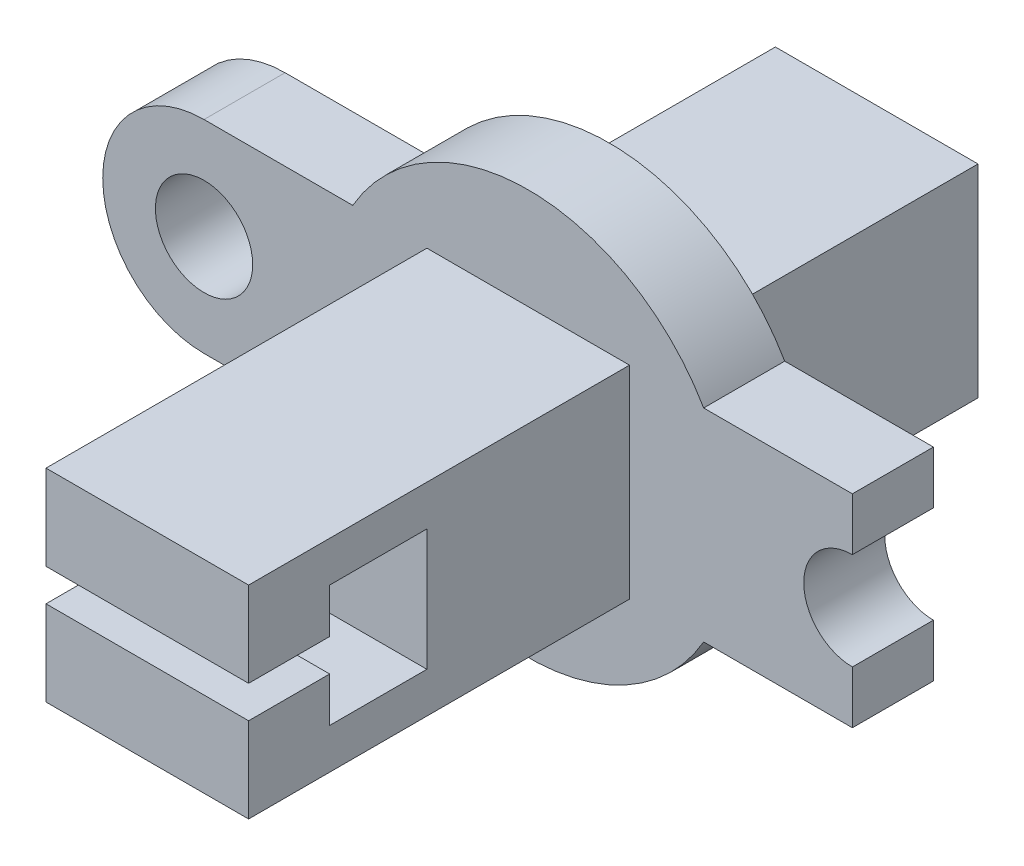
SolidWorks part; units mm, degrees
ref_plane "Спереди" through (0, 0, 0) normal (0, 0, 1) x (1, 0, 0)
ref_plane "Сверху" through (0, 0, 0) normal (0, 1, 0) x (1, 0, 0)
ref_plane "Справа" through (0, 0, 0) normal (1, 0, 0) x (0, 0, -1)
sketch "Эскиз1" plane through (0, 0, 0) normal (0, 0, 1) x (1, 0, 0)
  line L0 (-40, 12.5) -> (-21.6506, 12.5)
  line L1 (-12.5, -12.5) -> (12.5, -12.5)
  line L2 (-12.5, -12.5) -> (-12.5, 12.5)
  line L3 (-12.5, 12.5) -> (12.5, 12.5)
  line L4 (12.5, -12.5) -> (12.5, 12.5)
  line L5 (-12.5, -12.5) -> (12.5, 12.5) construction
  line L6 (-12.5, 12.5) -> (12.5, -12.5) construction
  line L7 (-40, -12.5) -> (-21.6506, -12.5)
  line L8 (0, 0) -> (0, 25) construction
  line L9 (40, -12.5) -> (21.6506, -12.5)
  line L10 (40, 12.5) -> (21.6506, 12.5)
  line L11 (40, -6) -> (40, -12.5)
  line L12 (40, 6) -> (40, 12.5)
  circle A0 centre (0, 0) radius 25
  circle A1 centre (-40, 0) radius 12.5
  circle A2 centre (-40, 0) radius 6
  circle A3 centre (40, 0) radius 6
  circle A4 centre (40, 0) radius 12.5
  circle A5 centre (0, -25) radius 5
  point P0 (0, 0)
  dimension "D2" = 50
  dimension "D3" = 25
  dimension "D5" = 12
  dimension "D6" = 10
  dimension "D1" = 25
  dimension "D4" = 40
extrude "Бобышка-Вытянуть1" add sketch "Эскиз1" along normal blind 90 contours L1 L4 L3 L2 region at (0, 0, 0)
extrude "Бобышка-Вытянуть2" add sketch "Эскиз1<3>" along normal blind 10 from offset 33 contours A0 L4 L1 L2 L3 | A1 L7 A0 L0 | A1 A2 | L9 A4 L10 A0 | A4 L11 A3 L12 | A0 A5 region at (-30.8253, 12.1899, 0) region at (-31.4112, 8.5888, 0) region at (0, 24.2964, 0) region at (30.8253, 12.1899, 0) region at (33.869, 0, 0) region at (0, -22.7904, 0)
sketch "Эскиз1<3>" plane through (0, 0, 0) normal (0, 0, 1) x (1, 0, 0) same geometry as "Эскиз1"
sketch "Эскиз3" plane through (12.5, 0, 0) normal (-1, 0, 0) x (0, 0, 1)
  line L0 (90, -12.5) -> (90, 12.5) construction
  line L1 (68, 7.5) -> (80, 7.5)
  line L2 (68, 7.5) -> (68, -7.5)
  line L3 (68, -7.5) -> (80, -7.5)
  line L4 (80, 7.5) -> (80, -7.5)
  line L5 (68, 7.5) -> (80, -7.5) construction
  line L6 (68, -7.5) -> (80, 7.5) construction
  line L7 (80, 2) -> (90, 2)
  line L8 (80, 2) -> (80, -2)
  line L9 (80, -2) -> (90, -2)
  line L10 (90, 2) -> (90, -2)
  line L11 (80, 2) -> (90, -2) construction
  line L12 (80, -2) -> (90, 2) construction
  point P0 (74, 0)
  point P5 (85, 0)
  dimension "D1" = 12
  dimension "D2" = 15
  dimension "D3" = 10
  dimension "D4" = 4
extrude "Вырез-Вытянуть3" cut sketch "Эскиз3" along normal through all contours L4 L3 L2 L1 | L7 L10 L9 L8
